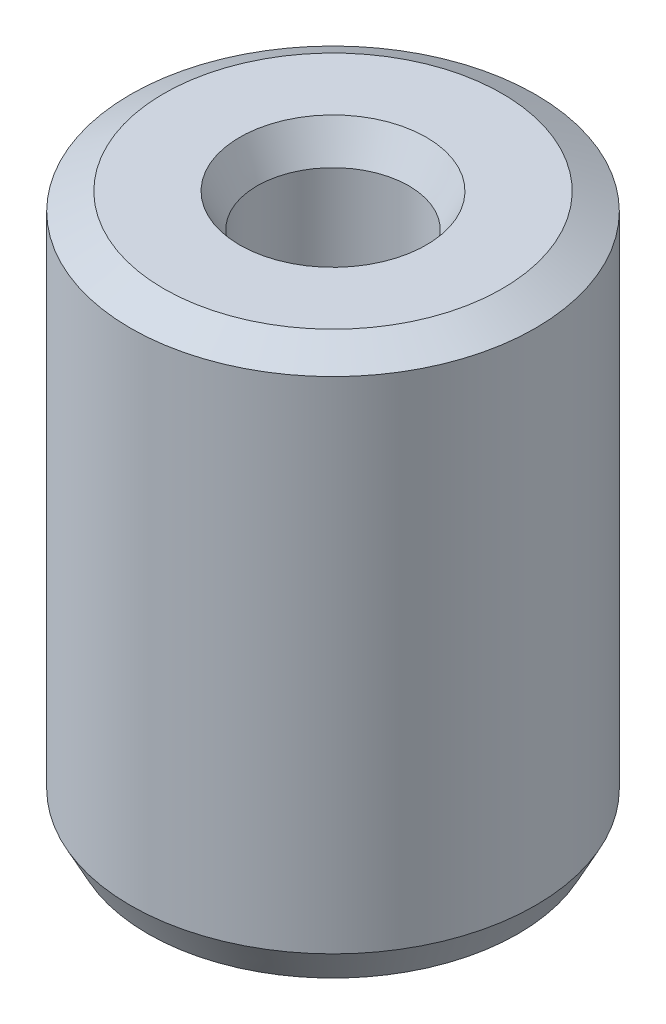
SolidWorks part; units mm, degrees
ref_plane "Front Plane" through (0, 0, 0) normal (0, 0, 1) x (1, 0, 0)
ref_plane "Top Plane" through (0, 0, 0) normal (0, 1, 0) x (1, 0, 0)
ref_plane "Right Plane" through (0, 0, 0) normal (1, 0, 0) x (0, 0, -1)
sketch "Sketch1" plane through (0, 0, 0) normal (0, 1, 0) x (1, 0, 0)
  circle A0 centre (0, 0) radius 22.5
  dimension "SLEEVE_OD" = 45
extrude "Boss-Extrude1" add sketch "Sketch1" along normal blind 61.2046
sketch "Sketch2" plane through (0, 0, 0) normal (0, 1, 0) x (1, 0, 0)
  circle A0 centre (0, 0) radius 8.4313
  dimension "BORE_D" = 16.8625
extrude "Cut-Extrude1" cut sketch "Sketch2" along normal through all
chamfer "Chamfer1" distance 1.9422 angle 62.326 4 edges at (0, 61.2046, 8.4313) (0, 0, 8.4313) (0, 0, 22.5) (0, 61.2046, 22.5) first distance on face at (0, 61.2046, 8.4313) first distance on face at (0, 0, 8.4313) first distance on face at (0, 61.2046, 22.5)
